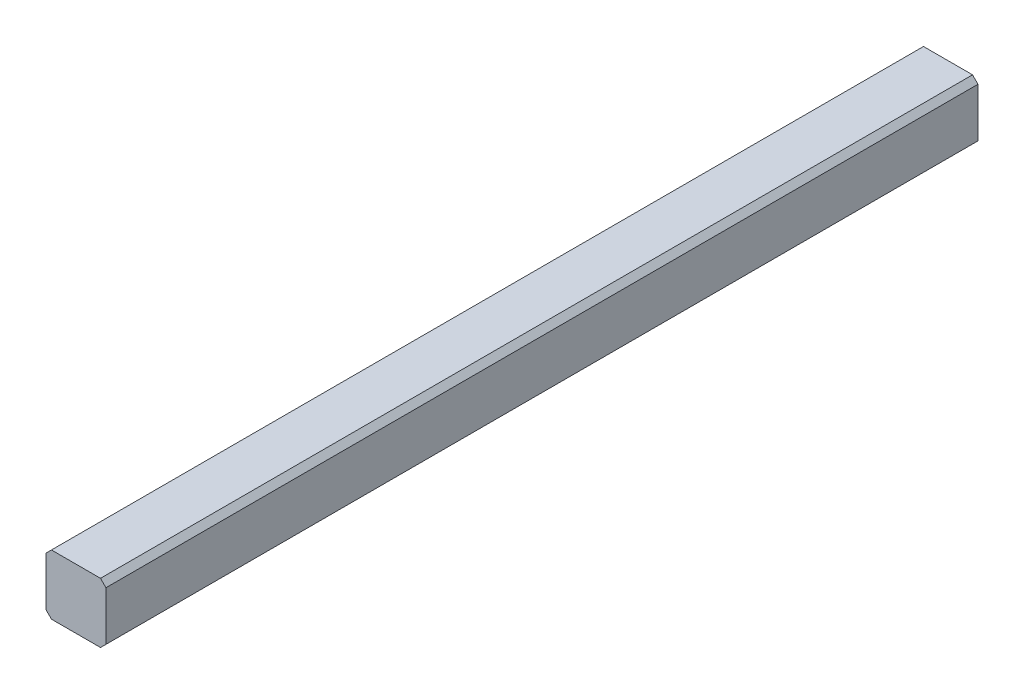
SolidWorks part; units mm, degrees
ref_plane "Front" through (0, 0, 0) normal (0, 0, 1) x (1, 0, 0)
ref_plane "Top" through (0, 0, 0) normal (0, 1, 0) x (1, 0, 0)
ref_plane "Right" through (0, 0, 0) normal (1, 0, 0) x (0, 0, -1)
sketch "Esquisse1" plane through (0, 0, 0) normal (0, 0, 1) x (1, 0, 0)
  line L1 (0, 0) -> (55, 0)
  line L2 (0, 0) -> (0, 55)
  line L3 (0, 55) -> (55, 55)
  line L4 (55, 0) -> (55, 55)
  dimension "D1" = 55
  dimension "D2" = 55
extrude "Boss.-Extru.1" add sketch "Esquisse1" along normal blind 800
sketch "Esquisse2" plane through (0, 0, 0) normal (0, -1, 0) x (1, 0, 0)
  line L0 (27.5, 0) -> (27.5, 160) construction
  line L1 (0, 0) -> (55, 0) construction
  line L2 (27.5, 175) -> (27.5, 145) construction
  line L3 (35.5, 175) -> (35.5, 145)
  line L4 (19.5, 175) -> (19.5, 145)
  line L5 (27.5, 800) -> (27.5, 750) construction
  line L6 (0, 800) -> (55, 800) construction
  line L7 (27.5, 735) -> (27.5, 765) construction
  line L8 (19.5, 735) -> (19.5, 765)
  line L9 (35.5, 735) -> (35.5, 765)
  arc A0 (35.5, 175) -> (19.5, 175) centre (27.5, 175) ccw
  arc A1 (19.5, 145) -> (35.5, 145) centre (27.5, 145) ccw
  arc A2 (19.5, 735) -> (35.5, 735) centre (27.5, 735) ccw
  arc A3 (35.5, 765) -> (19.5, 765) centre (27.5, 765) ccw
  point P6 (27.5, 160)
  point P17 (27.5, 750)
  dimension "D1" = 16
  dimension "D2" = 30
  dimension "D3" = 160
  dimension "D4" = 590
extrude "Enlèv. mat.-Extru.1" cut sketch "Esquisse2" against normal blind 30
sketch "Esquisse3" plane through (55, 0, 0) normal (1, 0, 0) x (0, 0, -1)
  line L0 (0, 27.5) -> (-160, 27.5) construction
  line L1 (0, 0) -> (0, 55) construction
  line L2 (-175, 27.5) -> (-145, 27.5) construction
  line L3 (-175, 35.5) -> (-145, 35.5)
  line L4 (-175, 19.5) -> (-145, 19.5)
  line L5 (-800, 27.5) -> (-750, 27.5) construction
  line L6 (-800, 0) -> (-800, 55) construction
  line L7 (-765, 27.5) -> (-735, 27.5) construction
  line L8 (-765, 35.5) -> (-735, 35.5)
  line L9 (-765, 19.5) -> (-735, 19.5)
  arc A0 (-175, 35.5) -> (-175, 19.5) centre (-175, 27.5) ccw
  arc A1 (-145, 19.5) -> (-145, 35.5) centre (-145, 27.5) ccw
  arc A2 (-765, 35.5) -> (-765, 19.5) centre (-765, 27.5) ccw
  arc A3 (-735, 19.5) -> (-735, 35.5) centre (-735, 27.5) ccw
  point P6 (-160, 27.5)
  point P17 (-750, 27.5)
  dimension "D1" = 16
  dimension "D2" = 30
  dimension "D3" = 160
  dimension "D4" = 590
extrude "Enlèv. mat.-Extru.2" [suppressed] cut sketch "Esquisse3" against normal blind 30
extrude "Enlèv. mat.-Extru.3" cut sketch "Esquisse3<2>" along normal blind 30 from vertex starting at point (0, 0, 0)
sketch "Esquisse3<2>" plane through (55, 0, 0) normal (1, 0, 0) x (0, 0, -1) same geometry as "Esquisse3"
chamfer "Chanfrein1" distance 5 angle 45 4 edges at (0, 55, 400) (55, 55, 400) (55, 0, 400) (0, 0, 400)
sketch "Esquisse5" [suppressed] plane through (0, 0, 0) normal (0, -1, 0) x (1, 0, 0)
  line L0 (35, 800) -> (35, 420) construction
  line L1 (5, 800) -> (50, 800) construction
  line L3 (55, 800) -> (55, 0) construction
  circle A0 centre (35, 420) radius 5
  dimension "D1" = 10
  dimension "D2" = 380
  dimension "D3" = 20
extrude "Enlèv. mat.-Extru.5" [suppressed] cut sketch "Esquisse5" against normal blind 20
